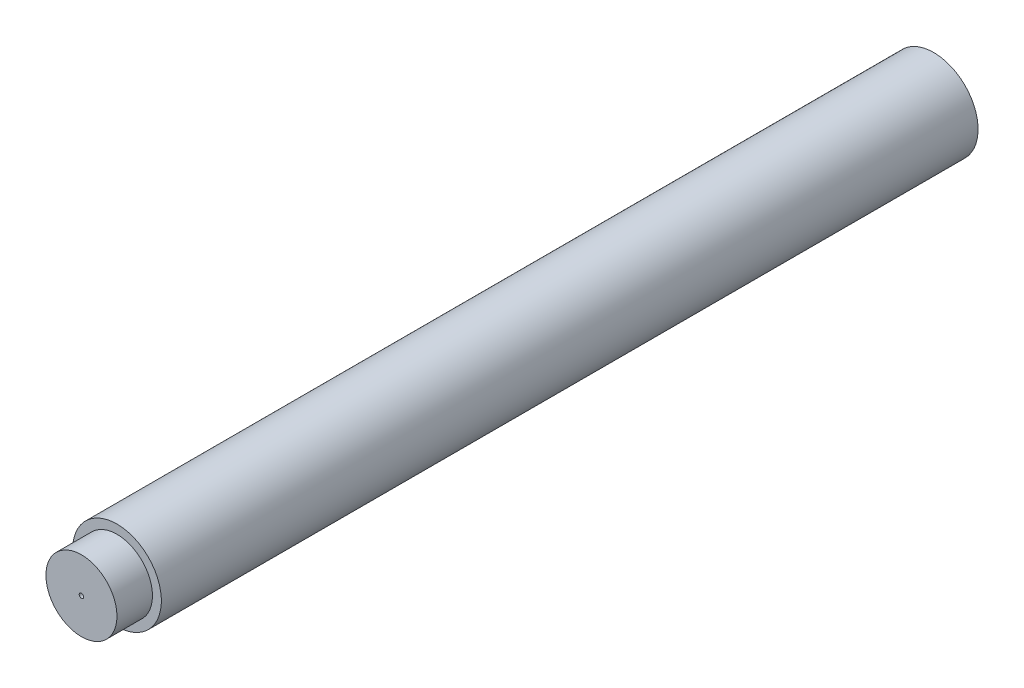
SolidWorks part; units mm, degrees
ref_plane "Front Plane" through (0, 0, 0) normal (0, 0, 1) x (1, 0, 0)
ref_plane "Top Plane" through (0, 0, 0) normal (0, 1, 0) x (1, 0, 0)
ref_plane "Right Plane" through (0, 0, 0) normal (1, 0, 0) x (0, 0, -1)
sketch "Sketch1" plane through (0, 0, 0) normal (0, 0, 1) x (1, 0, 0)
  line L1 (-7.9375, 0) -> (7.9375, 0) construction
sketch "Sketch2" plane through (0, 0, 0) normal (1, 0, 0) x (0, 0, -1)
  line L0 (76.2, 0) -> (-76.2, 0)
  point P4 (0, 0)
sketch "Sketch3" plane through (0, 0, 0) normal (0, 0, 1) x (1, 0, 0)
  circle A0 centre (0, 0) radius 7.9375
  dimension "D1" = 15.875
extrude "Boss-Extrude1" add sketch "Sketch3" along normal mid plane 152.4
sketch "Sketch4" plane through (0, 0, 0) normal (1, 0, 0) x (0, 0, -1)
  line L0 (76.2, 0) -> (-76.2, 0) construction
  line L1 (-76.2, 7.9375) -> (-76.2, -7.9375) construction
  point P0 (-58.3406, 0)
  point P6 (0, 0)
  point P8 (-52.3875, 0)
  point P9 (52.3875, 0)
  point P10 (58.3406, 0)
  dimension "D1" = 17.8594
  dimension "D2" = 23.8125
  dimension "D3" = 17.8594
  dimension "D4" = 23.8125
sketch "Sketch5" plane through (0, 0, 76.2) normal (0, 0, 1) x (1, 0, 0)
  circle A0 centre (0, 0) radius 6.35
extrude "Cut-Extrude1" cut sketch "Sketch5" against normal blind 6.35 flip side to cut contours A0
sketch "Sketch6" plane through (0, 0, -76.2) normal (0, 0, -1) x (-1, 0, 0)
  circle A0 centre (0, 0) radius 0.3969
extrude "Cut-Extrude2" cut sketch "Sketch6" against normal blind 152.4 contours A0
fillet "Fillet5" radius 3.4925 1 edges at (-0.3969, 0, -76.2) second distance 12.7 conic rho 0.2 first distance on face at (-0.3969, 0, -76.2)
equation "\"D1@Boss-Extrude1\"=\"Length@Sketch2\""
equation "\"D1@Sketch4\"=\"OD@Sketch1\"*1.125"
equation "\"D2@Sketch4\"=\"OD@Sketch1\"*1.5"
equation "\"D3@Sketch4\"=\"D1@Sketch4\""
equation "\"D4@Sketch4\"=\"D2@Sketch4\""
